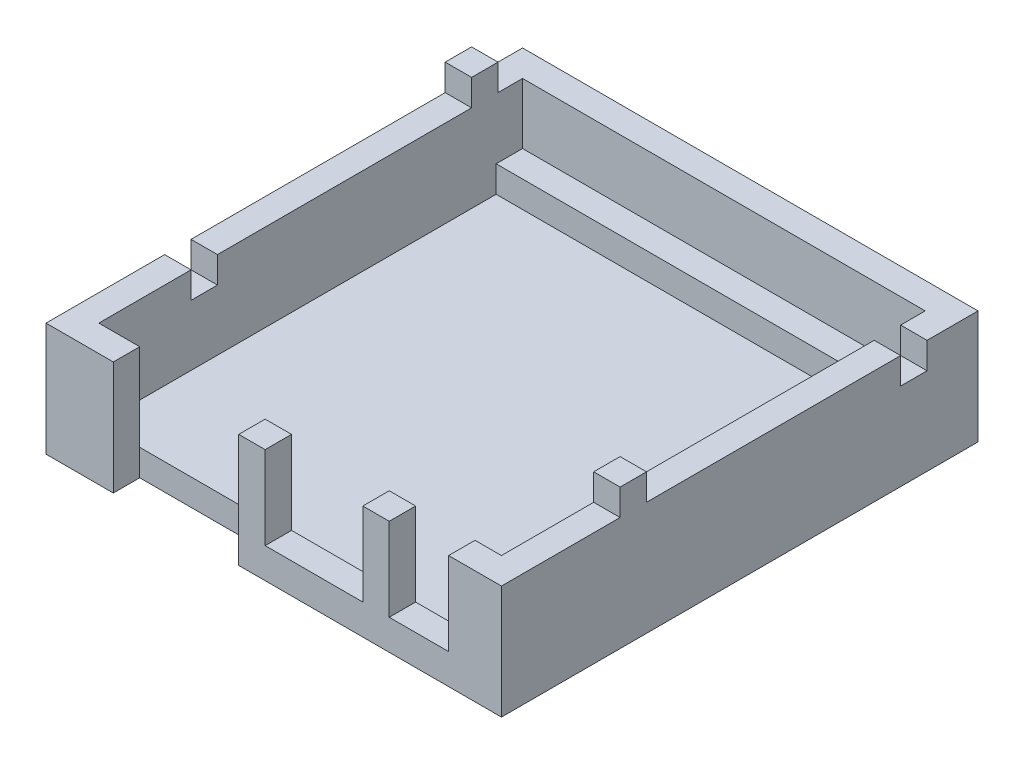
SolidWorks part; units mm, degrees
ref_plane "Front Plane" through (0, 0, 0) normal (0, 0, 1) x (1, 0, 0)
ref_plane "Top Plane" through (0, 0, 0) normal (0, 1, 0) x (1, 0, 0)
ref_plane "Right Plane" through (0, 0, 0) normal (1, 0, 0) x (0, 0, -1)
sketch "Sketch3" plane through (0, 0, 0) normal (0, 1, 0) x (1, 0, 0)
  line L1 (0, 0) -> (34.5, 0)
  line L2 (0, 0) -> (0, -36.1)
  line L3 (0, -36.1) -> (34.5, -36.1)
  line L4 (34.5, 0) -> (34.5, -36.1)
  dimension "D1" = 36.1
  dimension "D2" = 34.5
extrude "Shell" add sketch "Sketch3" along normal blind 8.6
sketch "Sketch4" plane through (0, 8.6, 0) normal (0, 1, 0) x (1, 0, 0)
  line L0 (34.5, 0) -> (0, 0) construction
  line L1 (2, -4) -> (32.5, -4)
  line L2 (2, -4) -> (2, -34.1)
  line L3 (2, -34.1) -> (32.5, -34.1)
  line L4 (32.5, -4) -> (32.5, -34.1)
  line L5 (34.5, -36.1) -> (34.5, 0) construction
  line L6 (0, 0) -> (0, -36.1) construction
  line L7 (0, -36.1) -> (34.5, -36.1) construction
  dimension "D1" = 4
  dimension "D2" = 2
  dimension "D3" = 2
  dimension "D4" = 2
extrude "Main Cavity" cut sketch "Sketch4" against normal offset from surface (6.6 mm away) 2 up to face at (17.25, 0, 18.05)
sketch "Sketch5" plane through (0, 8.6, 0) normal (0, 1, 0) x (1, 0, 0)
  line L0 (32.5, -34.1) -> (32.5, -4) construction
  line L1 (2, -4) -> (32.5, -4)
  line L2 (2, -4) -> (2, -2)
  line L3 (2, -2) -> (32.5, -2)
  line L4 (32.5, -4) -> (32.5, -2)
  dimension "D1" = 2
extrude "Support Shelf" cut sketch "Sketch5" against normal offset from surface (4.6 mm away) 2 up to face at (17.25, 2, 19.05)
sketch "Sketch6" plane through (0, 0, 36.1) normal (0, 0, 1) x (1, 0, 0)
  line L0 (0, 0) -> (34.5, 0) construction
  line L2 (30.5, 2.3) -> (30.5, 8.6)
  line L3 (30.5, 8.6) -> (26, 8.6)
  line L5 (0, 8.6) -> (34.5, 8.6) construction
  line L7 (24, 2.3) -> (24, 8.6)
  line L8 (24, 8.6) -> (16.6, 8.6)
  line L9 (16.6, 2.3) -> (16.6, 8.6)
  line L10 (14.6, 0) -> (5.1, 0)
  line L11 (14.6, 0) -> (14.6, 8.6)
  line L12 (14.6, 8.6) -> (5.1, 8.6)
  line L13 (5.1, 0) -> (5.1, 8.6)
  line L15 (16.6, 2.3) -> (24, 2.3)
  line L16 (26, 8.6) -> (26, 2.3)
  line L17 (26, 2.3) -> (30.5, 2.3)
  line L18 (34.5, 8.6) -> (34.5, 0) construction
  dimension "D1" = 4
  dimension "D2" = 4.5
  dimension "D3" = 7.4
  dimension "D4" = 2
  dimension "D5" = 2
  dimension "D6" = 9.5
  dimension "D7" = 2.3
  dimension "D8" = 2.3
extrude "Terminal Input" cut sketch "Sketch6" against normal up to surface (2 mm away) up to face at (17.25, 5.3, 34.1)
sketch "Sketch7" plane through (0, 8.6, 0) normal (0, 1, 0) x (1, 0, 0)
  line L0 (34.5, -36.1) -> (34.5, 0) construction
  line L1 (32.5, -25.113) -> (34.5, -25.113)
  line L2 (32.5, -25.113) -> (32.5, -27.113)
  line L3 (32.5, -27.113) -> (34.5, -27.113)
  line L4 (34.5, -25.113) -> (34.5, -27.113)
  line L5 (0, -3.8597) -> (2, -3.8597)
  line L6 (0, -3.8597) -> (0, -5.8597)
  line L7 (0, -5.8597) -> (2, -5.8597)
  line L8 (2, -3.8597) -> (2, -5.8597)
  line L9 (32.5, -34.1) -> (32.5, -2) construction
  line L10 (2, -2) -> (2, -34.1) construction
  line L11 (0, 0) -> (0, -36.1) construction
  dimension "D1" = 2
  dimension "D2" = 2
extrude "Male Tabs" add sketch "Sketch7" along normal blind 2
sketch "Sketch8" plane through (0, 8.6, 0) normal (0, 1, 0) x (1, 0, 0)
  line L0 (2, -3.8597) -> (0, -3.8597) construction
  line L1 (32.5, -3.8597) -> (34.5, -3.8597)
  line L2 (32.5, -3.8597) -> (32.5, -5.8597)
  line L3 (32.5, -5.8597) -> (34.5, -5.8597)
  line L4 (34.5, -3.8597) -> (34.5, -5.8597)
  line L5 (0, -25.113) -> (2, -25.113)
  line L6 (0, -25.113) -> (0, -27.113)
  line L7 (0, -27.113) -> (2, -27.113)
  line L8 (2, -25.113) -> (2, -27.113)
  line L9 (34.5, -25.113) -> (34.5, 0) construction
  line L11 (32.5, -4) -> (32.5, -34.1) construction
  line L12 (0, -5.8597) -> (0, -36.1) construction
  line L13 (2, -5.8597) -> (2, -34.1) construction
  line L14 (32.5, -27.113) -> (34.5, -27.113) construction
  dimension "D1" = 2
  dimension "D2" = 2
extrude "Female Tabs" cut sketch "Sketch8" against normal blind 2
